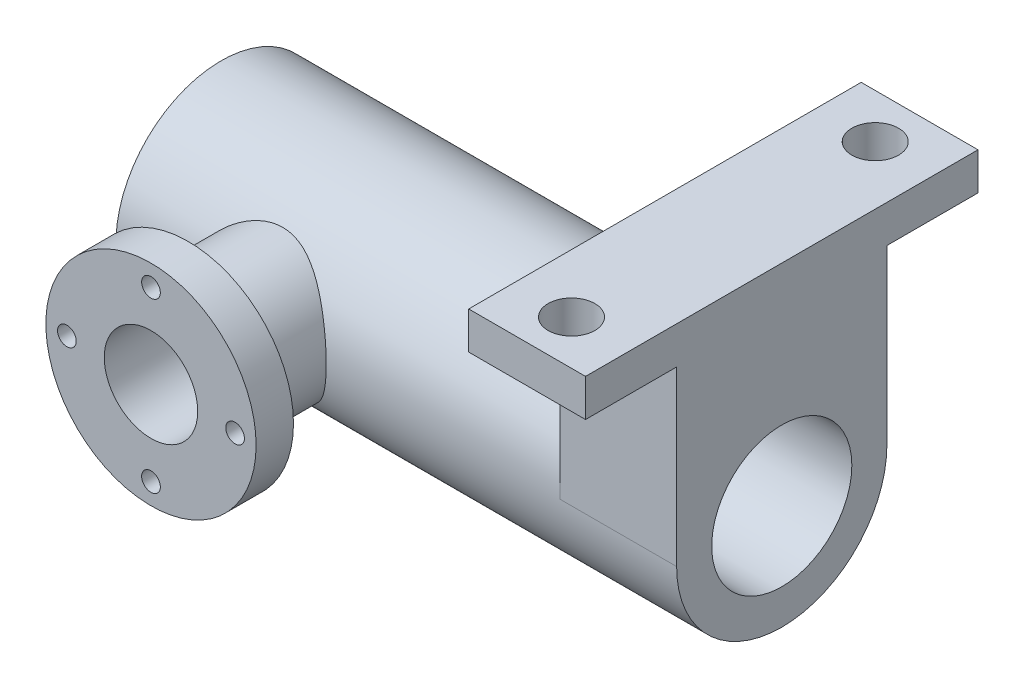
SolidWorks part; units mm, degrees
ref_plane "前视基准面" through (0, 0, 0) normal (0, 0, 1) x (1, 0, 0)
ref_plane "上视基准面" through (0, 0, 0) normal (0, 1, 0) x (1, 0, 0)
ref_plane "右视基准面" through (0, 0, 0) normal (1, 0, 0) x (0, 0, -1)
other "Configuration Table"
sketch "草图1" plane through (0, 0, 0) normal (1, 0, 0) x (0, 0, -1)
  circle A0 centre (0, 0) radius 22.5
  circle A1 centre (0, 0) radius 15
  dimension "D1" = 30
  dimension "D2" = 45
extrude "凸台-拉伸1" add sketch "草图1" along normal blind 120
sketch "草图2" plane through (0, 0, 0) normal (0, 1, 0) x (1, 0, 0)
  line L0 (120, -42) -> (120, 42)
  line L1 (120, 42) -> (95, 42)
  line L2 (95, 42) -> (95, -42)
  line L3 (95, -42) -> (120, -42)
  line L4 (120, -22.5) -> (120, 22.5) construction
  line L5 (-45.0789, 0) -> (165.4257, 0) construction
  line L6 (95, 22.5) -> (120, 22.5)
  line L7 (120, 22.5) -> (0, 22.5) construction
  line L8 (95, -22.5) -> (120, -22.5)
  line L9 (0, -22.5) -> (120, -22.5) construction
  line L10 (95, 15) -> (107.5, 15)
  line L11 (107.5, 15) -> (107.5, -15)
  line L12 (95, -15) -> (107.5, -15)
  circle A0 centre (107.5, 32.5) radius 5
  circle A1 centre (107.5, -32.5) radius 5
  point P25 (107.5, 0)
  dimension "D5" = 10
  dimension "D1" = 84
  dimension "D2" = 25
  dimension "D3" = 12.5
  dimension "D4" = 12.5
  dimension "D6" = 65
  dimension "D7" = 30
extrude "凸台-拉伸5" add sketch "草图2" against normal blind 8 from offset 45 separate body contours L11 L5 L0 L6 L2 L10 | L5 L11 L12 L2 L8 L0 | L8 L2 L3 L0 A1 | L2 L6 L0 L1 A0 | L2 L5 L11 L10 | L5 L2 L12 L11 region at (107.5, 0, 41.6829) region at (110.625, 0, 13.125) region at (110.625, 0, -13.125) region at (107.5, 0, -22.8171) region at (101.25, 0, 7.5) region at (101.25, 0, -7.5)
extrude "凸台-拉伸6" add sketch "草图2<7>" against normal up to body from offset 37 separate body contours L5 L11 L12 L2 L8 L0 | L11 L5 L0 L6 L2 L10 region at (110.625, 0, 13.125) region at (110.625, 0, -13.125)
sketch "草图2<7>" plane through (0, 0, 0) normal (0, 1, 0) x (1, 0, 0) same geometry as "草图2"
sketch "草图3" plane through (0, 0, 0) normal (0, 0, 1) x (1, 0, 0)
  line L0 (-18.3757, 0) -> (124.1571, 0) construction
  circle A0 centre (30, 0) radius 10
  circle A1 centre (30, 0) radius 15
  circle A2 centre (30, 0) radius 22.5
  point P7 (0, 0)
  dimension "D1" = 20
  dimension "D2" = 30
  dimension "D3" = 45
  dimension "D4" = 30
extrude "凸台-拉伸7" add sketch "草图3" against normal blind 8 from offset 45 separate body contours A2 L0 A1 | L0 A2 A1 | L0 A1 A0 | A1 L0 A0 region at (30, 10.3354, 0) region at (42.5, -0.3354, 0) region at (30, 15.5031, 0) region at (48.75, -0.5031, 0)
extrude "凸台-拉伸8" add sketch "草图3<3>" against normal up to body from offset 37 separate body contours L0 A1 A0 | A1 L0 A0 region at (30, 10.3354, 0) region at (42.5, -0.3354, 0)
sketch "草图3<3>" plane through (0, 0, 0) normal (0, 0, 1) x (1, 0, 0) same geometry as "草图3"
extrude "切除-拉伸1" cut sketch "草图3<4>" along normal up to next separate body contours A0
sketch "草图3<4>" plane through (0, 0, 0) normal (0, 0, 1) x (1, 0, 0) same geometry as "草图3"
sketch "草图4" plane through (0, 0, 45) normal (0, 0, 1) x (1, 0, 0)
  line L0 (30, 0) -> (30, 36) construction
  line L1 (30, 0) -> (30, -20.9141) construction
  circle A0 centre (30, 0) radius 18 construction
  circle A1 centre (30, 18) radius 2
  circle A2 centre (48, 0) radius 2
  circle A3 centre (30, -18) radius 2
  circle A4 centre (12, 0) radius 2
  point P15 (30, 0)
  dimension "D1" = 36
  dimension "D2" = 4
  dimension "D3" = 4
extrude "切除-拉伸2" cut sketch "草图4" against normal up to next
